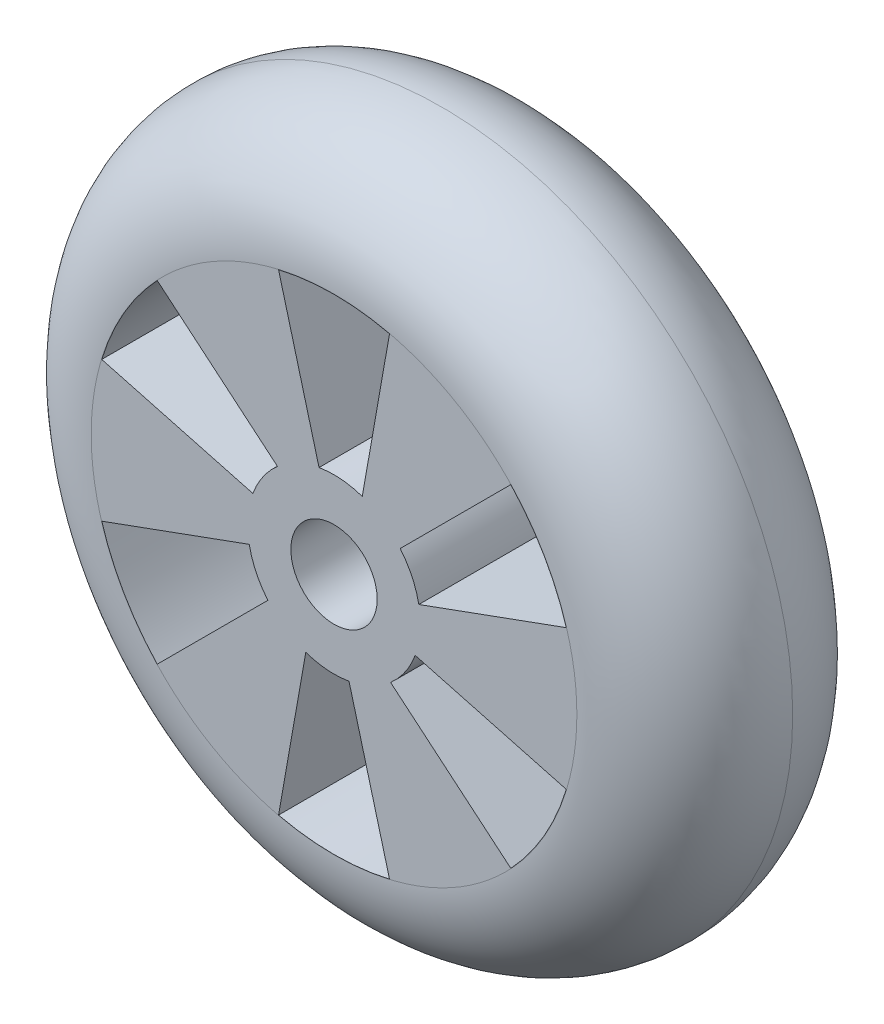
SolidWorks part; units mm, degrees
ref_plane "前视基准面" through (0, 0, 0) normal (0, 0, 1) x (1, 0, 0)
ref_plane "上视基准面" through (0, 0, 0) normal (0, 1, 0) x (1, 0, 0)
ref_plane "右视基准面" through (0, 0, 0) normal (1, 0, 0) x (0, 0, -1)
sketch "草图1" plane through (0, 0, 0) normal (0, 0, 1) x (1, 0, 0)
  circle A0 centre (0, 0) radius 32.5
  circle A1 centre (0, 0) radius 4
  dimension "D1" = 65
  dimension "D2" = 8
extrude "凸台-拉伸1" add sketch "草图1" along normal blind 20
fillet "圆角1" radius 10 2 edges at (32.5, 0, 0) (32.5, 0, 20)
sketch "草图2" plane through (0, 0, 20) normal (0, 0, 1) x (1, 0, 0)
  line L0 (0, 22.4804) -> (0, 8) construction
  line L1 (-5.1421, 21.8844) -> (-1.3892, 7.8785)
  line L2 (5.1421, 21.8844) -> (2.6163, 7.5601)
  arc A0 (5.1421, 21.8844) -> (-5.1421, 21.8844) centre (0, 0) ccw
  arc A1 (2.6163, 7.5601) -> (-1.3892, 7.8785) centre (0, 0) ccw
  dimension "D1" = 15
extrude "切除-拉伸1" cut sketch "草图2" against normal blind 20
ref_axis "基准轴1" through (0, 0, 20) along (0, 0, -1)
pattern_circular "阵列(圆周)1" count 6 over 360 about axis through (0, 0, 20) along (0, 0, -1) of "切除-拉伸1"
